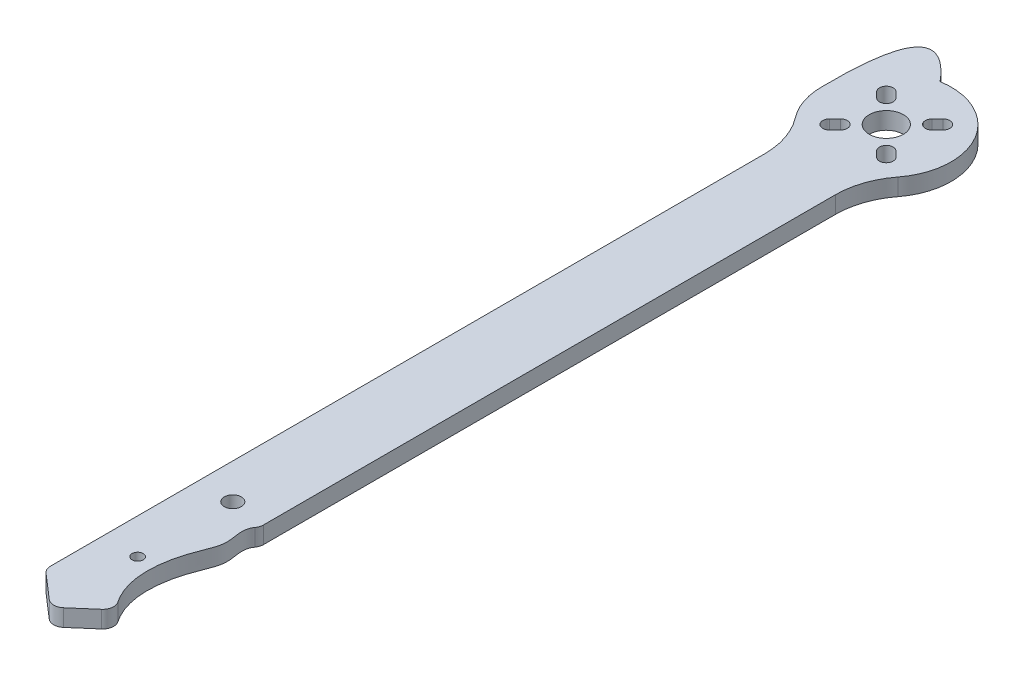
SolidWorks part; units mm, degrees
ref_plane "Front Plane" through (0, 0, 0) normal (0, 0, 1) x (1, 0, 0)
ref_plane "Top Plane" through (0, 0, 0) normal (0, 1, 0) x (1, 0, 0)
ref_plane "Right Plane" through (0, 0, 0) normal (1, 0, 0) x (0, 0, -1)
sketch "Sketch1" plane through (0, 0, 0) normal (0, 1, 0) x (1, 0, 0)
  line L0 (0, 0) -> (0, 209.55)
  line L1 (5.332, 189.1367) -> (6.5949, 187.8739) construction
  line L3 (-8.2352, 181.8344) -> (-8.2352, 0)
  line L4 (-8.2352, 0) -> (8.2352, 0)
  line L5 (8.2352, 181.8344) -> (8.2352, 0)
  line L6 (-6.4546, 190.2593) -> (-7.7174, 188.9964)
  line L7 (6.4546, 190.2593) -> (7.7174, 188.9964)
  line L8 (4.2095, 188.0142) -> (5.4723, 186.7513)
  line L9 (-4.2095, 188.0142) -> (-5.4723, 186.7513)
  line L10 (-5.332, 189.1367) -> (-6.5949, 187.8739) construction
  line L11 (-4.2095, 200.9233) -> (-5.4723, 202.1862)
  line L12 (-6.4546, 198.6782) -> (-7.7174, 199.9411)
  line L13 (-5.332, 199.8008) -> (-6.5949, 201.0636) construction
  line L14 (6.4546, 198.6782) -> (7.7174, 199.9411)
  line L15 (4.2095, 200.9233) -> (5.4723, 202.1862)
  line L16 (5.332, 199.8008) -> (6.5949, 201.0636) construction
  line L17 (-8.2352, 7.1437) -> (0, 0)
  line L18 (8.2352, 7.1437) -> (0, 0)
  line L19 (-8.2352, 7.1437) -> (8.2352, 7.1437)
  circle A0 centre (0, 194.4688) radius 3.9687
  circle A1 centre (0, 194.4688) radius 15.0812
  arc A2 (6.4546, 190.2593) -> (4.2095, 188.0142) centre (5.332, 189.1367) ccw
  arc A3 (5.4723, 186.7513) -> (7.7174, 188.9964) centre (6.5949, 187.8739) ccw
  arc A4 (-4.2095, 188.0142) -> (-6.4546, 190.2593) centre (-5.332, 189.1367) ccw
  arc A5 (-7.7174, 188.9964) -> (-5.4723, 186.7513) centre (-6.5949, 187.8739) ccw
  arc A6 (-6.4546, 198.6782) -> (-4.2095, 200.9233) centre (-5.332, 199.8008) ccw
  arc A7 (-5.4723, 202.1862) -> (-7.7174, 199.9411) centre (-6.5949, 201.0636) ccw
  arc A8 (4.2095, 200.9233) -> (6.4546, 198.6782) centre (5.332, 199.8008) ccw
  arc A9 (7.7174, 199.9411) -> (5.4723, 202.1862) centre (6.5949, 201.0636) ccw
  circle A10 centre (0, 42.4656) radius 1.9844
  circle A11 centre (0, 20.3398) radius 1.2898
  spline S0 degree 2 poles (-15.0812, 194.4688) (-15.5726, 225.0996) (-2.3852, 209.3602) knots 0 0 0 1 1 1
  spline S1 degree 3 poles (8.2352, 40.4439) (6.1597, 38.3778) (8.4485, 34.0777) (3.3122, 23.2306) (2.7642, 13.1947) (8.2352, 7.1437) knots 0 0 0 0 0.202238 0.355836 1 1 1 1
  point P14 (0, 0)
  point P16 (5.9635, 188.5053)
  point P24 (-5.9635, 188.5053)
  point P31 (-5.9635, 200.4322)
  point P38 (5.9635, 200.4322)
  point P48 (0, 0)
  dimension "D2" = 7.9375
  dimension "D6" = 4.9609
  dimension "D8" = 1.9844
  dimension "D11" = 3.9688
  dimension "D12" = 146.05
  dimension "D13" = 2.5797
  dimension "D14" = 18.8516
  dimension "D1" = 209.55
  dimension "D3" = 11.1125
  dimension "D5" = 16.4703
  dimension "D7" = 3.175
  dimension "D9" = 45
  dimension "D17" = 7.1437
  dimension "D4" = 11.1125
  dimension "D10" = 4
extrude "Boss-Extrude1" add sketch "Sketch1" along normal mid plane 3.9688 contours A11 L0 A10 A1 L3 L19 | S1 L5 A1 L0 A10 A11 L19 | L19 L17 L0 | L19 L0 L18 | L0 A1 A0 A7 L11 A6 L12 A5 L6 A4 L9 | L0 A1 A0 A9 L14 A8 L15 A3 L8 A2 L7 | S0 A1 region at (-2.7451, 0, -4.7625) region at (2.7451, 0, -4.7625) region at (-4.1481, 0, -94.0196) region at (3.9941, 0, -98.5397) region at (-6.8217, 0, -194.4688) region at (-10.2501, 0, -208.6785) region at (6.8217, 0, -194.4688)
fillet "Fillet1" radius 17.78 2 edges at (-8.2352, 0, -181.8344) (8.2352, 0, -181.8344)
fillet "Fillet3" radius 2.54 4 edges at (8.2352, 0, -40.4439) (-8.2352, 0, -7.1437) (0, 0, 0) (8.2352, 0, -7.1437)
